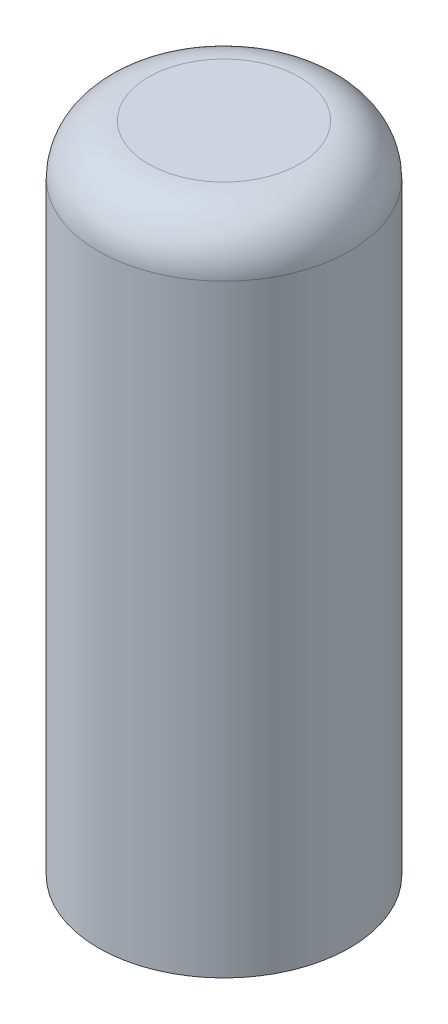
SolidWorks part; units mm, degrees
ref_plane "Front Plane" through (0, 0, 0) normal (0, 0, 1) x (1, 0, 0)
ref_plane "Top Plane" through (0, 0, 0) normal (0, 1, 0) x (1, 0, 0)
ref_plane "Right Plane" through (0, 0, 0) normal (1, 0, 0) x (0, 0, -1)
sketch "Sketch2" plane through (0, 0, 0) normal (0, 1, 0) x (1, 0, 0)
  circle A0 centre (0, 0) radius 2.5
  circle A1 centre (0, 0) radius 0.5
  dimension "D1" = 5
  dimension "D2" = 1
extrude "Boss-Extrude1" add sketch "Sketch2" along normal mid plane 13
fillet "Fillet1" radius 1 1 edges at (0, 6.5, 2.5)
sketch "Sketch3" plane through (0, 6.5, 0) normal (0, 1, 0) x (1, 0, 0)
  circle A0 centre (0, 0) radius 0.5 construction
  circle A1 centre (0, 0) radius 0.5
extrude "Boss-Extrude4" add sketch "Sketch3" against normal blind 1
